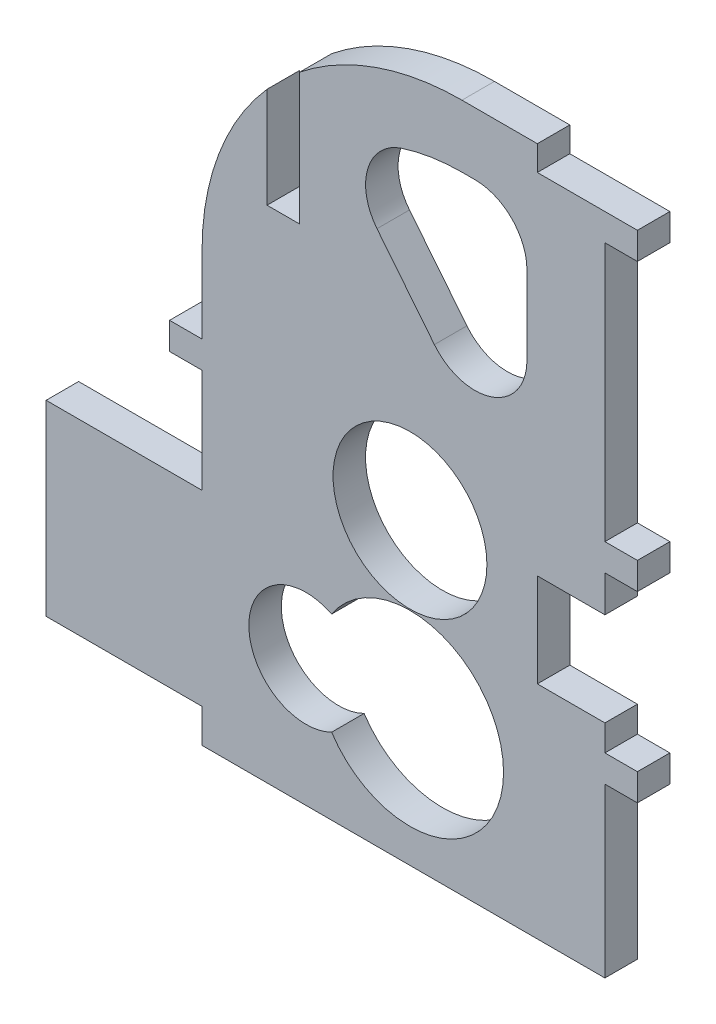
SolidWorks part; units mm, degrees
material "Balsa"
ref_plane "Front Plane" through (0, 0, 0) normal (0, 0, 1) x (1, 0, 0)
ref_plane "Top Plane" through (0, 0, 0) normal (0, 1, 0) x (1, 0, 0)
ref_plane "Right Plane" through (0, 0, 0) normal (1, 0, 0) x (0, 0, -1)
sketch "Sketch1" plane through (0, 0, 0) normal (0, 0, 1) x (1, 0, 0)
  line L0 (0, -1000) -> (0, 49000) construction
  line L1 (-1000, 0) -> (49000, 0) construction
  line L2 (0, -8.382) -> (-5.08, -8.382)
  line L3 (9.525, 16.51) -> (11.1125, 16.51)
  line L4 (2.54, 19.05) -> (9.525, 19.05)
  line L5 (9.525, -14.605) -> (-10.16, -14.605)
  line L6 (-10.16, -14.605) -> (-10.16, 6.35)
  line L7 (9.525, 19.05) -> (9.525, -14.605)
  line L8 (-11.7475, 1.27) -> (-10.16, 1.27)
  line L9 (-11.7475, 1.27) -> (-11.7475, 2.5908)
  line L10 (-11.7475, 2.5908) -> (-10.16, 2.5908)
  line L11 (-10.16, 1.27) -> (-10.16, 2.5908)
  line L12 (9.525, 2.54) -> (11.1125, 2.54)
  line L13 (9.525, 2.54) -> (9.525, 3.8608)
  line L14 (9.525, 3.8608) -> (11.1125, 3.8608)
  line L15 (11.1125, 2.54) -> (11.1125, 3.8608)
  line L16 (9.525, 16.51) -> (9.525, 17.8308)
  line L17 (9.525, 17.8308) -> (11.1125, 17.8308)
  line L18 (11.1125, 16.51) -> (11.1125, 17.8308)
  line L19 (-7.112, 6.35) -> (5.969, 6.35) construction
  line L20 (-10.16, -12.954) -> (-17.78, -12.954)
  line L21 (5.969, 6.35) -> (5.969, 16.002) construction
  line L22 (-10.16, -3.81) -> (-17.78, -3.81)
  line L23 (-17.78, -12.954) -> (-17.78, -3.81)
  line L24 (5.969, 16.002) -> (2.54, 16.002) construction
  line L27 (9.525, -6.4008) -> (11.1125, -6.4008)
  line L28 (9.525, -6.4008) -> (9.525, -5.08)
  line L29 (9.525, -5.08) -> (11.1125, -5.08)
  line L30 (11.1125, -6.4008) -> (11.1125, -5.08)
  circle A0 centre (0, 0) radius 3.7592
  arc A1 (-3.829, -10.8803) -> (-3.829, -5.8837) centre (0, -8.382) ccw
  arc A2 (-3.829, -5.8837) -> (-3.829, -10.8803) centre (-5.08, -8.382) ccw
  arc A3 (2.54, 19.05) -> (-10.16, 6.35) centre (2.54, 6.35) ccw
  arc A4 (2.54, 16.002) -> (-7.112, 6.35) centre (2.54, 6.35) ccw construction
  arc A5 (2.54, 19.05) -> (-10.16, 6.35) centre (2.54, 6.35) ccw construction
  dimension "D1" = 7.5184
  dimension "D4" = 9.144
  dimension "D3" = 19.685
  dimension "D5" = 8.382
  dimension "D9" = 12.7
  dimension "D10" = 1.5875
  dimension "D16" = 3.81
  dimension "D7" = 5.588
  dimension "D6" = 5.08
  dimension "D8" = 9.525
  dimension "D11" = 9.144
  dimension "D12" = 1.3208
  dimension "D13" = 1.3208
  dimension "D14" = 1.5875
  dimension "D15" = 2
  dimension "D17" = 14.605
  dimension "D18" = 19.05
  dimension "D19" = 16.51
  dimension "D20" = 3.048
  dimension "D21" = 3.556
  dimension "D22" = 1.3208
  dimension "D23" = 1.5875
  dimension "D24" = 5.08
  dimension "D25" = 1.27
  dimension "D26" = 7.62
  dimension "D27" = 2.54
extrude "Boss-Extrude1" add sketch "Sketch1" along normal blind 1.5875 contours L4 A3 L7 A0 | L10 L9 L8 | L3 L18 L17 L7 | L12 L15 L14 L7 | A3 | L27 L30 L29 L7 | L23 L20 L6 L22 region at (10.3187, 17.1704, 0) region at (9.1351, 10.1854, 0) region at (10.3187, 3.2004, 0) region at (10.3187, -5.7404, 0) region at (-10.9538, 1.9304, 0) region at (-13.97, -8.382, 0)
sketch "Sketch2" plane through (0, 0, 1.5875) normal (0, 0, 1) x (1, 0, 0)
  line L1 (6.223, -3.81) -> (9.525, -3.81)
  line L2 (6.223, -3.81) -> (6.223, 0.762)
  line L3 (6.223, 0.762) -> (9.525, 0.762)
  line L4 (9.525, -3.81) -> (9.525, 0.762)
  line L5 (9.525, 2.54) -> (9.525, -5.08) construction
  line L7 (9.525, 19.05) -> (9.525, 17.8308) construction
  line L9 (6.223, 17.8308) -> (9.525, 17.8308)
  line L10 (6.223, 17.8308) -> (6.223, 21.59)
  line L11 (6.223, 21.59) -> (9.525, 21.59)
  line L12 (9.525, 17.8308) -> (9.525, 21.59)
  line L13 (9.525, 17.8308) -> (11.1125, 17.8308) construction
  point P9 (9.525, -1.524)
  point P10 (9.525, 19.7104)
  point P15 (9.525, 19.7104)
  line M4 (9.525, 19.05) -> (2.54, 19.05)
  line M12 (9.525, -5.08) -> (9.525, 2.54)
  line M20 (9.525, 17.8308) -> (9.525, 19.05)
  dimension "D1" = 4.572
  dimension "D2" = 3.302
  dimension "D3" = 3.7592
  dimension "D4" = 3.302
  dimension "D5" = 0.762
extrude "Cut-Extrude1" cut sketch "Sketch2" against normal up to next contours L3 L2 L4 M12 | L10 L9 M20 M4 region at (7.874, -1.524, 1.5875) region at (7.874, 18.4404, 1.5875)
sketch "Sketch3" plane through (0, 0, 1.5875) normal (0, 0, 1) x (1, 0, 0)
  line L0 (-5.3975, 9.8425) -> (-6.985, 9.8425) construction
  line L1 (-5.3975, 16.2639) -> (-5.3975, 9.8425) construction
  line L2 (-6.985, 9.8425) -> (-6.985, 14.7503) construction
  line L3 (-5.3975, 9.8425) -> (-6.985, 9.8425)
  line L4 (-5.3975, 16.2639) -> (-5.3975, 9.8425)
  line L5 (-6.985, 9.8425) -> (-6.985, 14.7503)
  line L6 (-5.3975, 16.2639) -> (-6.985, 16.2639)
  line L7 (-6.985, 16.2639) -> (-6.985, 14.7503)
extrude "Cut-Extrude2" cut sketch "Sketch3" against normal through all
sketch "Sketch4" plane through (0, 0, 1.5875) normal (0, 0, 1) x (1, 0, 0)
  line L0 (3.175, 16.002) -> (2.54, 16.002) construction
  line L1 (3.175, 16.002) -> (2.54, 16.002)
  line L2 (-1.6119, 11.5357) -> (1.1922, 8.0334) construction
  line L3 (-1.6119, 11.5357) -> (1.1922, 8.0334)
  line L4 (5.715, 9.6209) -> (5.715, 13.462) construction
  line L5 (5.715, 9.6209) -> (5.715, 13.462)
  arc A0 (5.715, 13.462) -> (3.175, 16.002) centre (3.175, 13.462) ccw construction
  arc A1 (2.54, 16.002) -> (-0.4037, 15.5421) centre (2.54, 6.35) ccw construction
  arc A2 (-0.4037, 15.5421) -> (-1.6119, 11.5357) centre (0.3709, 13.1232) ccw construction
  arc A3 (5.715, 13.462) -> (3.175, 16.002) centre (3.175, 13.462) ccw
  arc A4 (2.54, 16.002) -> (-0.4037, 15.5421) centre (2.54, 6.35) ccw
  arc A5 (-0.4037, 15.5421) -> (-1.6119, 11.5357) centre (0.3709, 13.1232) ccw
  arc A6 (1.1922, 8.0334) -> (5.715, 9.6209) centre (3.175, 9.6209) ccw construction
  arc A7 (1.1922, 8.0334) -> (5.715, 9.6209) centre (3.175, 9.6209) ccw
extrude "Cut-Extrude3" cut sketch "Sketch4" against normal through all
